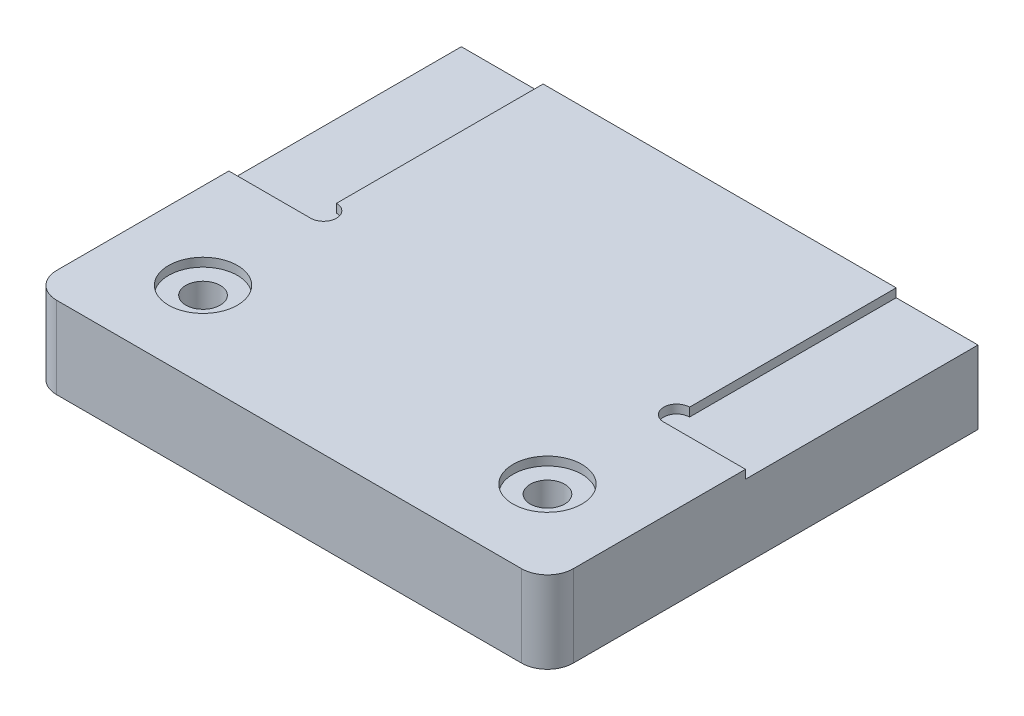
SolidWorks part; units mm, degrees
ref_plane "前视基准面" through (0, 0, 0) normal (0, 0, 1) x (1, 0, 0)
ref_plane "上视基准面" through (0, 0, 0) normal (0, 1, 0) x (1, 0, 0)
ref_plane "右视基准面" through (0, 0, 0) normal (1, 0, 0) x (0, 0, -1)
sketch "草图1" plane through (0, 0, 0) normal (0, 1, 0) x (1, 0, 0)
  line L1 (-30, 25) -> (30, 25)
  line L2 (-30, 25) -> (-30, -25)
  line L3 (-30, -25) -> (30, -25)
  line L4 (30, 25) -> (30, -25)
  line L5 (-30, 25) -> (30, -25) construction
  line L6 (-30, -25) -> (30, 25) construction
  point P0 (0, 0)
  dimension "D1" = 60
  dimension "D2" = 50
extrude "凸台-拉伸1" add sketch "草图1" along normal blind 9.5
fillet "圆角1" radius 3 2 edges at (-30, 4.75, 25) (30, 4.75, 25)
sketch "草图2" plane through (0, 9.5, 0) normal (0, 1, 0) x (1, 0, 0)
  line L0 (0, 0) -> (0, -25) construction
  line L1 (-27, -25) -> (27, -25) construction
  circle A0 centre (-20, -15) radius 4
  circle A1 centre (20, -15) radius 4
  dimension "D1" = 8
  dimension "D2" = 40
  dimension "D3" = 10
extrude "切除-拉伸1" cut sketch "草图2" against normal blind 1 contours A1 | A0
sketch "草图4" plane through (0, 9.5, 0) normal (0, 1, 0) x (1, 0, 0)
  line L9 (-30, 25) -> (-20.5, 25)
  line L10 (-30, 25) -> (-30, -2)
  line L11 (-30, -2) -> (-20.5, -2)
  line L12 (-20.5, 25) -> (-20.5, 1)
  line L13 (20.5, -2) -> (30, -2)
  line L14 (20.5, 1) -> (20.5, 25)
  line L15 (20.5, 25) -> (30, 25)
  line L16 (30, -2) -> (30, 25)
  arc A2 (-20.5, -2) -> (-20.5, 1) centre (-20.5, -0.5) ccw
  arc A3 (20.5, 1) -> (20.5, -2) centre (20.5, -0.5) ccw
  dimension "D1" = 3
extrude "切除-拉伸2" cut sketch "草图4" against normal blind 1
sketch "草图5" plane through (0, 9.5, 0) normal (0, 1, 0) x (1, 0, 0)
  circle A0 centre (-20, -15) radius 2
  circle A1 centre (20, -15) radius 2
  dimension "D1" = 4
extrude "切除-拉伸3" cut sketch "草图5" against normal through all
